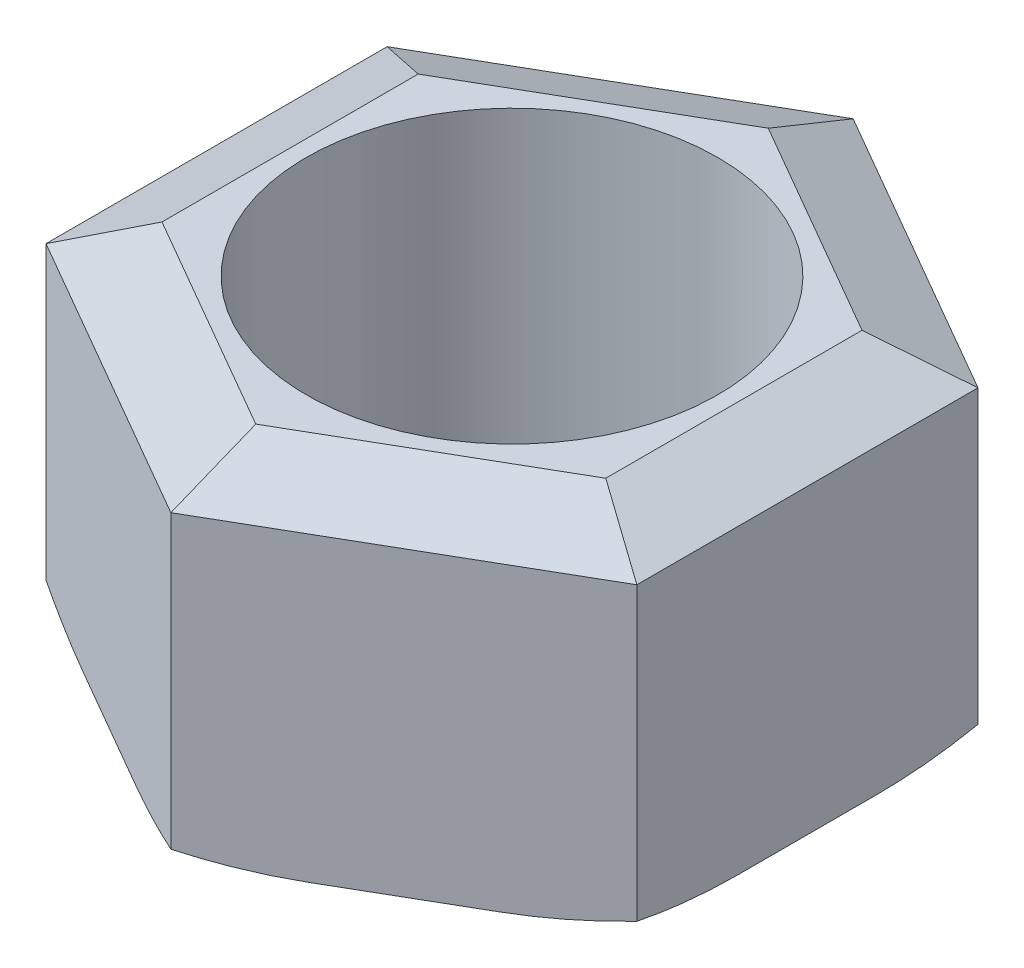
SolidWorks part; units mm, degrees
ref_plane "Спереди" through (0, 0, 0) normal (0, 0, 1) x (1, 0, 0)
ref_plane "Сверху" through (0, 0, 0) normal (0, 1, 0) x (1, 0, 0)
ref_plane "Справа" through (0, 0, 0) normal (1, 0, 0) x (0, 0, -1)
sketch "Эскиз1" plane through (0, 0, 0) normal (0, 1, 0) x (1, 0, 0)
  line L1 (0, 9.95) -> (-8.617, 4.975)
  line L2 (-8.617, 4.975) -> (-8.617, -4.975)
  line L3 (-8.617, -4.975) -> (0, -9.95)
  line L4 (0, -9.95) -> (8.617, -4.975)
  line L5 (8.617, -4.975) -> (8.617, 4.975)
  line L6 (8.617, 4.975) -> (0, 9.95)
  circle A0 centre (0, 0) radius 9.95 construction
  circle A1 centre (0, 0) radius 6
extrude "Бобышка-Вытянуть1" add sketch "Эскиз1" along normal blind 10.8
chamfer "Фаска1" distance 1 angle 65 6 edges at (8.617, 10.8, 0) (4.3085, 10.8, -7.4625) (-4.3085, 10.8, -7.4625) (-8.617, 10.8, 0) (-4.3085, 10.8, 7.4625) (4.3085, 10.8, 7.4625) first distance on face at (8.617, 5.4, 0) first distance on face at (4.3085, 5.4, -7.4625) first distance on face at (-4.3085, 5.4, -7.4625) first distance on face at (-8.617, 5.4, 0) first distance on face at (-4.3085, 5.4, 7.4625) first distance on face at (4.3085, 5.4, 7.4625)
chamfer "Фаска2" distance 1 angle 65 6 edges at (-4.3085, 0, -7.4625) (4.3085, 0, -7.4625) (8.617, 0, 0) (4.3085, 0, 7.4625) (-4.3085, 0, 7.4625) (-8.617, 0, 0) tangent propagation no first distance on face at (-4.3085, 4.9, -7.4625) first distance on face at (4.3085, 4.9, -7.4625) first distance on face at (8.617, 4.9, 0) first distance on face at (4.3085, 4.9, 7.4625) first distance on face at (-4.3085, 4.9, 7.4625) first distance on face at (-8.617, 4.9, 0)
fillet "Скругление2" radius 12 6 edges at (0, 0.5, -8.7119) (-7.5447, 0.5, -4.3559) (-7.5447, 0.5, 4.3559) (0, 0.5, 8.7119) (7.5447, 0.5, 4.3559) (7.5447, 0.5, -4.3559)
